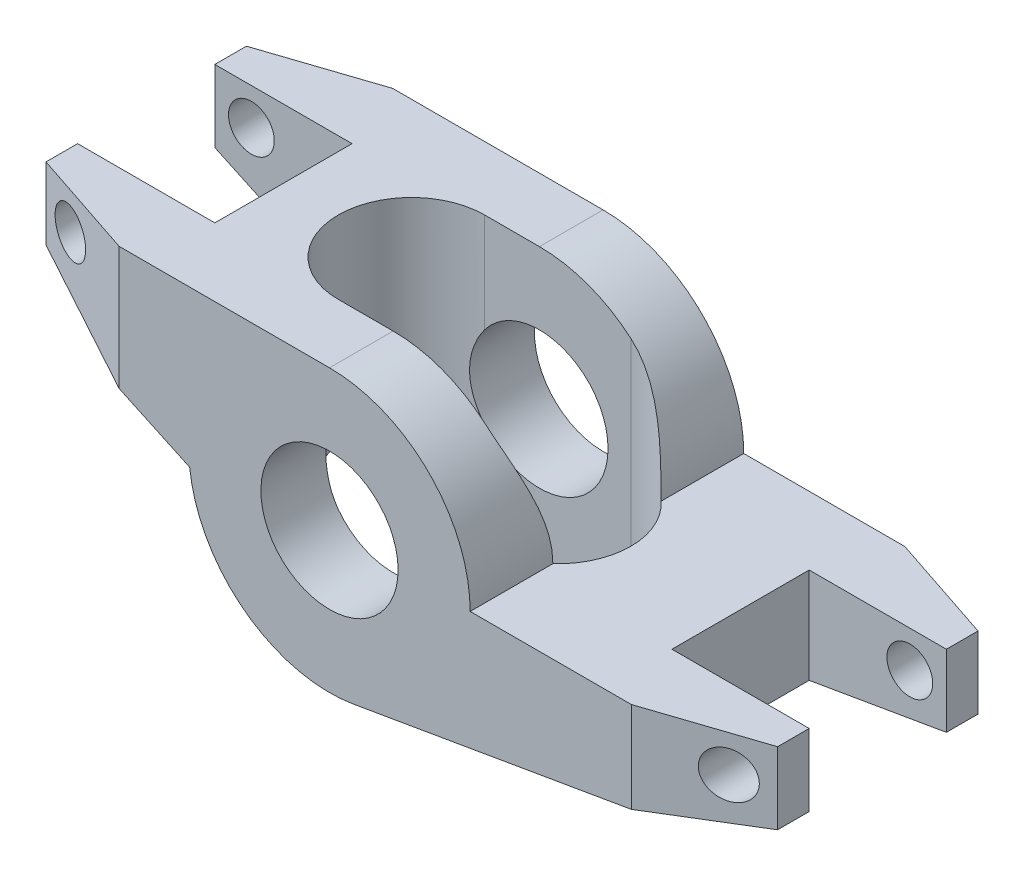
SolidWorks part; units mm, degrees
material "Alloy Steel"
ref_plane "Front Plane" through (0, 0, 0) normal (0, 0, 1) x (1, 0, 0)
ref_plane "Top Plane" through (0, 0, 0) normal (0, 1, 0) x (1, 0, 0)
ref_plane "Right Plane" through (0, 0, 0) normal (1, 0, 0) x (0, 0, -1)
sketch "Sketch2" plane through (0, 0, 0) normal (0, 0, 1) x (1, 0, 0)
  line L0 (0, 9.77) -> (-22.23, 9.77)
  line L1 (-22.23, 9.77) -> (-22.23, 4.77)
  line L2 (-22.23, 4.77) -> (-9.7115, -1.0675)
  line L3 (9.77, 0) -> (28.58, 0)
  line L4 (28.58, 0) -> (28.58, -5)
  line L5 (28.58, -5) -> (1.6553, -9.6287)
  circle A0 centre (0, 0) radius 4.765
  arc A1 (-9.7115, -1.0675) -> (1.6553, -9.6287) centre (0, 0) ccw
  arc A2 (9.77, 0) -> (0, 9.77) centre (0, 0) ccw
  dimension "D1" = 19.54
  dimension "D2" = 9.53
  dimension "D3" = 22.23
  dimension "D4" = 5
  dimension "D5" = 25
  dimension "D6" = 5
  dimension "D7" = 28.58
extrude "Boss-Extrude1" add sketch "Sketch2" along normal mid plane 19
sketch "Sketch3" plane through (0, 9.77, 0) normal (0, 1, 0) x (1, 0, 0)
  line L0 (-22.23, -9.5) -> (-22.23, 9.5) construction
  line L1 (-22.23, 4.765) -> (-12.7, 4.765)
  line L2 (-22.23, 4.765) -> (-22.23, -4.765)
  line L3 (-22.23, -4.765) -> (-12.7, -4.765)
  line L4 (-12.7, 4.765) -> (-12.7, -4.765)
  line L5 (28.58, -9.5) -> (28.58, 9.5) construction
  line L6 (28.58, 4.765) -> (19.05, 4.765)
  line L7 (28.58, 4.765) -> (28.58, -4.765)
  line L8 (28.58, -4.765) -> (19.05, -4.765)
  line L9 (19.05, 4.765) -> (19.05, -4.765)
  point P12 (-12.7, 0)
  point P14 (19.05, 0)
  dimension "D1" = 9.53
  dimension "D2" = 9.53
extrude "Cut-Extrude1" cut sketch "Sketch3" against normal through all
sketch "Sketch4" plane through (0, 9.77, 0) normal (0, 1, 0) x (1, 0, 0)
  line L0 (-3.81, 0) -> (6.35, 0) construction
  line L1 (-3.81, 5.08) -> (6.35, 5.08)
  line L2 (-3.81, -5.08) -> (6.35, -5.08)
  line L3 (-12.7, -4.765) -> (-12.7, 4.765) construction
  arc A0 (-3.81, 5.08) -> (-3.81, -5.08) centre (-3.81, 0) ccw
  arc A1 (6.35, -5.08) -> (6.35, 5.08) centre (6.35, 0) ccw
  point P3 (1.27, 0)
  dimension "D3" = 5.08
  dimension "D1" = 8.89
  dimension "D2" = 10.16
extrude "Cut-Extrude2" cut sketch "Sketch4" against normal through all
sketch "Sketch5" plane through (0, 0, 9.5) normal (0, 0, 1) x (1, 0, 0)
  line L0 (0, 9.77) -> (-22.23, 9.77) construction
  line L1 (-22.23, 9.77) -> (-22.23, 4.77) construction
  line L2 (28.58, -5) -> (28.58, 0) construction
  line L3 (28.58, 0) -> (9.77, 0) construction
  circle A0 centre (-19.69, 7.23) radius 1.59
  circle A1 centre (26.04, -2.54) radius 1.59
  dimension "D1" = 3.18
  dimension "D2" = 2.54
  dimension "D3" = 2.54
  dimension "D4" = 2.54
  dimension "D5" = 2.54
extrude "Cut-Extrude3" cut sketch "Sketch5" against normal through all
chamfer "Chamfer1" distance 7.62 distance2 2.54 2 edges at (28.58, -2.5, -9.5) (-22.23, 7.27, -9.5) first distance on face at (-18.1, 7.23, -9.5)
chamfer "Chamfer2" distance 2.54 distance2 7.62 2 edges at (28.58, -2.5, 9.5) (-22.23, 7.27, 9.5) first distance on face at (28.58, -2.5, 7.1325) first distance on face at (-22.23, 7.27, 7.1325)
